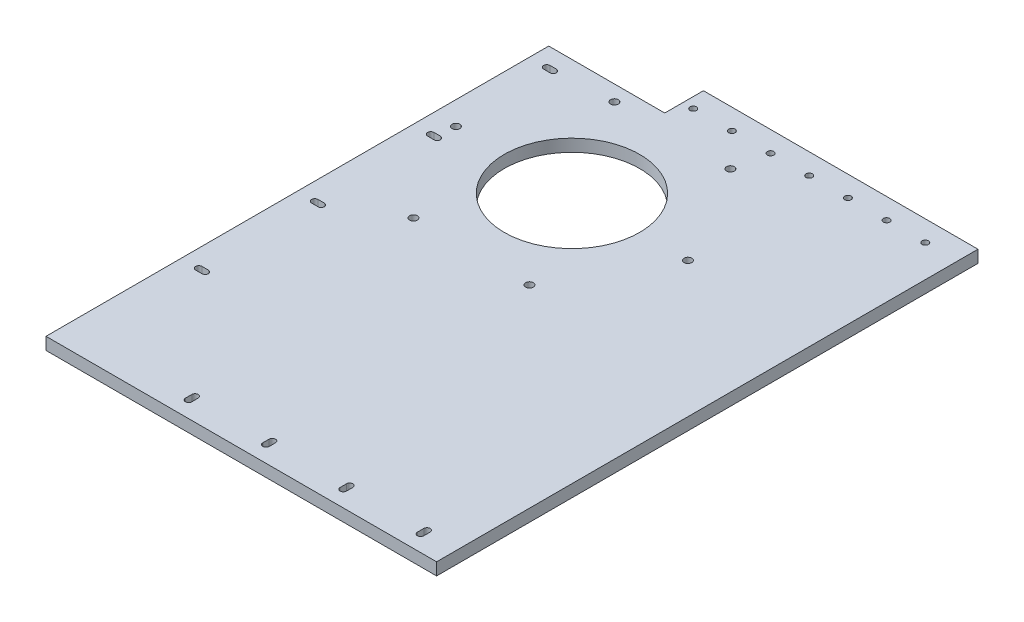
SolidWorks part; units mm, degrees
ref_plane "Front Plane" through (0, 0, 0) normal (0, 0, 1) x (1, 0, 0)
ref_plane "Top Plane" through (0, 0, 0) normal (0, 1, 0) x (1, 0, 0)
ref_plane "Right Plane" through (0, 0, 0) normal (1, 0, 0) x (0, 0, -1)
sketch "Sketch1" plane through (0, 0, 0) normal (0, 1, 0) x (1, 0, 0)
  line L3 (-71, 140) -> (71, 140)
  line L4 (71, -140) -> (71, 140)
  line L5 (0, 140) -> (0, -135) construction
  line L6 (0, 0) -> (71, 0) construction
  line L10 (-71, 140) -> (-71, 120)
  line L11 (-71, 120) -> (-131, 120)
  line L12 (-131, 120) -> (-131, -140)
  line L13 (-131, -140) -> (71, -140)
  point P0 (0, 0)
  dimension "D1" = 280
  dimension "D2" = 20
  dimension "D3" = 202
  dimension "D4" = 60
extrude "Boss-Extrude1" add sketch "Sketch1" along normal blind 6.35
sketch "Sketch2" plane through (0, 6.35, 0) normal (0, 1, 0) x (1, 0, 0)
  line L1 (0, 140) -> (0, -140) construction
  line L2 (71, 140) -> (-71, 140) construction
  line L3 (-131, -140) -> (71, -140) construction
  circle A0 centre (0, -65) radius 41.5 construction
  circle A1 centre (0, -23.5) radius 2.25
  circle A2 centre (29.3449, -35.6551) radius 2.25
  circle A3 centre (41.5, -65) radius 2.25
  circle A4 centre (29.3449, -94.3449) radius 2.25
  circle A5 centre (0, -106.5) radius 2.25
  circle A6 centre (-29.3449, -94.3449) radius 2.25
  circle A7 centre (-41.5, -65) radius 2.25
  circle A8 centre (-29.3449, -35.6551) radius 2.25
  circle A9 centre (0, -65) radius 80 construction
  circle A10 centre (0, -65) radius 30
  point P22 (0, -65)
  dimension "D1" = 83
  dimension "D2" = 4.5
  dimension "D4" = 160
  dimension "D6" = 60
  dimension "D5" = 75
  dimension "D3" = 8
extrude "Cut-Extrude1" [suppressed] cut sketch "Sketch2" against normal through all
sketch "Sketch6" [suppressed] plane through (0, 6.35, 0) normal (0, 1, 0) x (1, 0, 0)
  line L0 (0, -65) -> (-38.9712, -46.8274) construction
  line L1 (0, -65) -> (0, -23.5) construction
  line L2 (-40.9787, -51.1324) -> (-36.9638, -42.5225) construction
  line L3 (-36.9638, -42.5225) -> (-27.9007, -46.7486) construction
  circle A0 centre (0, -65) radius 30 construction
  circle A1 centre (-36.9638, -42.5225) radius 0.85
  circle A2 centre (-40.9787, -51.1324) radius 0.85
  circle A5 centre (-29.9082, -51.0536) radius 0.85
  point P7 (-38.9712, -46.8274)
  dimension "D4" = 1.7
  dimension "D5" = 10
  dimension "D7" = 10
  dimension "D6" = 1.7
  dimension "D1" = 43
  dimension "D2" = 9.5
  dimension "D3" = 65
extrude "Cut-Extrude5" [suppressed] cut sketch "Sketch6" against normal through all
sketch "Sketch8" [suppressed] plane through (0, 6.35, 0) normal (0, 1, 0) x (1, 0, 0)
  line L1 (71, 140) -> (-71, 140) construction
  line L2 (65, -20.6305) -> (65, 140) construction
  line L3 (71, -140) -> (71, 140) construction
  line L5 (45, 41.8036) -> (45, 140) construction
  circle A0 centre (0, 65) radius 25
  circle A1 centre (0, -65) radius 30 construction
  dimension "D1" = 130
  dimension "D2" = 50
  dimension "D3" = 6
  dimension "D4" = 20
extrude "Cut-Extrude9" [suppressed] cut sketch "Sketch8" against normal through all
sketch "Sketch9" plane through (0, 0, 0) normal (0, -1, 0) x (-1, 0, 0)
  circle A1 centre (45.6, 129.325) radius 1.65
  circle A2 centre (5.6, 129.325) radius 1.65
  circle A3 centre (-34.4, 129.325) radius 1.65
  circle A4 centre (65.6, 129.325) radius 1.65
  circle A5 centre (25.6, 129.325) radius 1.65
  circle A6 centre (-14.4, 129.325) radius 1.65
  circle A7 centre (-54.4, 129.325) radius 1.65
extrude "Cut-Extrude10" cut sketch "Sketch9" against normal blind 30
sketch "Sketch10" plane through (0, 0, 0) normal (0, -1, 0) x (1, 0, 0)
  line L0 (-121.975, 10) -> (-118.675, 10) construction
  line L3 (-121.975, 11.65) -> (-118.675, 11.65)
  line L4 (-121.975, 8.35) -> (-118.675, 8.35)
  line L5 (-121.975, 70) -> (-118.675, 70) construction
  line L6 (-121.975, 71.65) -> (-118.675, 71.65)
  line L7 (-121.975, 68.35) -> (-118.675, 68.35)
  line L8 (-121.975, -50) -> (-118.675, -50) construction
  line L9 (-121.975, -48.35) -> (-118.675, -48.35)
  line L10 (-121.975, -51.65) -> (-118.675, -51.65)
  line L11 (-121.975, -110) -> (-118.675, -110) construction
  line L12 (-121.975, -108.35) -> (-118.675, -108.35)
  line L13 (-121.975, -111.65) -> (-118.675, -111.65)
  circle A0 centre (-120.325, -110) radius 1.65
  circle A1 centre (-120.325, -50) radius 1.65
  circle A2 centre (-120.325, 10) radius 1.65
  circle A3 centre (-120.325, 70) radius 1.65
  arc A6 (-121.975, 11.65) -> (-121.975, 8.35) centre (-121.975, 10) ccw
  arc A7 (-118.675, 8.35) -> (-118.675, 11.65) centre (-118.675, 10) ccw
  arc A8 (-121.975, 71.65) -> (-121.975, 68.35) centre (-121.975, 70) ccw
  arc A9 (-118.675, 68.35) -> (-118.675, 71.65) centre (-118.675, 70) ccw
  arc A10 (-121.975, -48.35) -> (-121.975, -51.65) centre (-121.975, -50) ccw
  arc A11 (-118.675, -51.65) -> (-118.675, -48.35) centre (-118.675, -50) ccw
  arc A12 (-121.975, -108.35) -> (-121.975, -111.65) centre (-121.975, -110) ccw
  arc A13 (-118.675, -111.65) -> (-118.675, -108.35) centre (-118.675, -110) ccw
  point P14 (-120.325, 10)
  point P21 (-120.325, 70)
  point P28 (-120.325, -50)
  point P35 (-120.325, -110)
  dimension "D1" = 3.3
  dimension "D2" = 3.3
  dimension "D3" = 3.3
  dimension "D4" = 3.3
  dimension "D5" = 1.65
  dimension "D6" = 1.65
  dimension "D7" = 1.65
  dimension "D8" = 1.65
sketch "Sketch11" plane through (0, 6.35, 0) normal (0, 1, 0) x (1, 0, 0)
  line L0 (71, -127.15) -> (-131, -127.15) construction
  line L1 (71, -140) -> (71, 140) construction
  line L2 (456.625, -127.15) -> (-127.825, -127.15) construction
  line L3 (-131, 120) -> (-131, -140) construction
  line L4 (71, -132.85) -> (-131, -132.85) construction
  line L5 (456.625, -132.85) -> (-127.825, -132.85) construction
  line L6 (-65.6, 129.325) -> (-65.6, -130.005) construction
  line L7 (-65.6, -130.005) -> (71, -130) construction
  line L8 (456.625, -130) -> (-127.825, -130) construction
  line L9 (-25.6, 129.325) -> (-25.6, -130.0035) construction
  line L10 (14.4, 129.325) -> (14.4, -130.0021) construction
  line L11 (54.4, 129.325) -> (54.4, -130.0006) construction
  line L12 (-65.6, -128.355) -> (-65.6, -131.655) construction
  line L13 (-63.95, -128.355) -> (-63.95, -131.655)
  line L14 (-67.25, -128.355) -> (-67.25, -131.655)
  line L15 (-25.6, -128.3535) -> (-25.6, -131.6535) construction
  line L16 (-23.95, -128.3535) -> (-23.95, -131.6535)
  line L17 (-27.25, -128.3535) -> (-27.25, -131.6535)
  line L18 (14.4, -128.3521) -> (14.4, -131.6521) construction
  line L19 (16.05, -128.3521) -> (16.05, -131.6521)
  line L20 (12.75, -128.3521) -> (12.75, -131.6521)
  line L21 (54.4, -128.3506) -> (54.4, -131.6506) construction
  line L22 (56.05, -128.3506) -> (56.05, -131.6506)
  line L23 (52.75, -128.3506) -> (52.75, -131.6506)
  circle A0 centre (-65.6, -130.005) radius 1.65 construction
  circle A1 centre (-25.6, -130.0035) radius 1.65 construction
  circle A2 centre (14.4, -130.0021) radius 1.65 construction
  circle A3 centre (54.4, -130.0006) radius 1.65 construction
  arc A4 (-63.95, -128.355) -> (-67.25, -128.355) centre (-65.6, -128.355) ccw
  arc A5 (-67.25, -131.655) -> (-63.95, -131.655) centre (-65.6, -131.655) ccw
  arc A6 (-23.95, -128.3535) -> (-27.25, -128.3535) centre (-25.6, -128.3535) ccw
  arc A7 (-27.25, -131.6535) -> (-23.95, -131.6535) centre (-25.6, -131.6535) ccw
  arc A8 (16.05, -128.3521) -> (12.75, -128.3521) centre (14.4, -128.3521) ccw
  arc A9 (12.75, -131.6521) -> (16.05, -131.6521) centre (14.4, -131.6521) ccw
  arc A10 (56.05, -128.3506) -> (52.75, -128.3506) centre (54.4, -128.3506) ccw
  arc A11 (52.75, -131.6506) -> (56.05, -131.6506) centre (54.4, -131.6506) ccw
  point P33 (-65.6, -130.005)
  point P39 (-25.6, -130.0035)
  point P46 (14.4, -130.0021)
  point P53 (54.4, -130.0006)
  dimension "D2" = 3.3
  dimension "D1" = 259.33
extrude "Cut-Extrude12" cut sketch "Sketch11" against normal blind 30
extrude "Cut-Extrude13" cut sketch "Sketch10" against normal blind 10 contours A0 | L13 A13 L12 A0 | L12 A12 L13 A0 | L9 A10 L10 A1 | A1 | L10 A11 L9 A1 | L3 A6 L4 A2 | A2 | L4 A7 L3 A2 | L6 A8 L7 A3 | A3 | L7 A9 L6 A3 region at (-122.4459, 0, 10) region at (-118.2041, 0, 10) region at (-120.325, 0, 10) region at (-122.4459, 0, 70) region at (-118.2041, 0, 70) region at (-120.325, 0, 70) region at (-122.4459, 0, -50) region at (-118.2041, 0, -50) region at (-120.325, 0, -50) region at (-122.4459, 0, -110) region at (-118.2041, 0, -110) region at (-120.325, 0, -110)
sketch "Sketch12" plane through (0, 6.35, 0) normal (0, 1, 0) x (1, 0, 0)
  line L0 (-131, -140) -> (71, -140) construction
  line L1 (71, -140) -> (71, 140) construction
  circle A0 centre (-59, 60) radius 35
  dimension "D1" = 70
  dimension "D2" = 200
  dimension "D3" = 130
extrude "Cut-Extrude14" cut sketch "Sketch12" against normal through all
sketch "Sketch13" plane through (0, 6.35, 0) normal (0, 1, 0) x (1, 0, 0)
  line L0 (-124, 60) -> (-114, 60) construction
  circle A2 centre (-59, 60) radius 65 construction
  circle A3 centre (-119, 60) radius 2
  circle A4 centre (-89, 111.9615) radius 2
  circle A5 centre (-59, 60) radius 65 construction
  circle A6 centre (-29, 111.9615) radius 2
  circle A7 centre (-59, 60) radius 65 construction
  circle A8 centre (1, 60) radius 2
  circle A9 centre (-59, 60) radius 65 construction
  circle A10 centre (-29, 8.0385) radius 2
  circle A11 centre (-59, 60) radius 65 construction
  circle A12 centre (-89, 8.0385) radius 2
  circle A13 centre (-59, 60) radius 65 construction
  circle A14 centre (-59, 60) radius 55 construction
  circle A15 centre (-59, 60) radius 35 construction
  point P25 (-59, 60)
  dimension "D1" = 130
  dimension "D2" = 4
  dimension "D3" = 6
  dimension "D4" = 110
extrude "Cut-Extrude15" cut sketch "Sketch13" against normal through all
